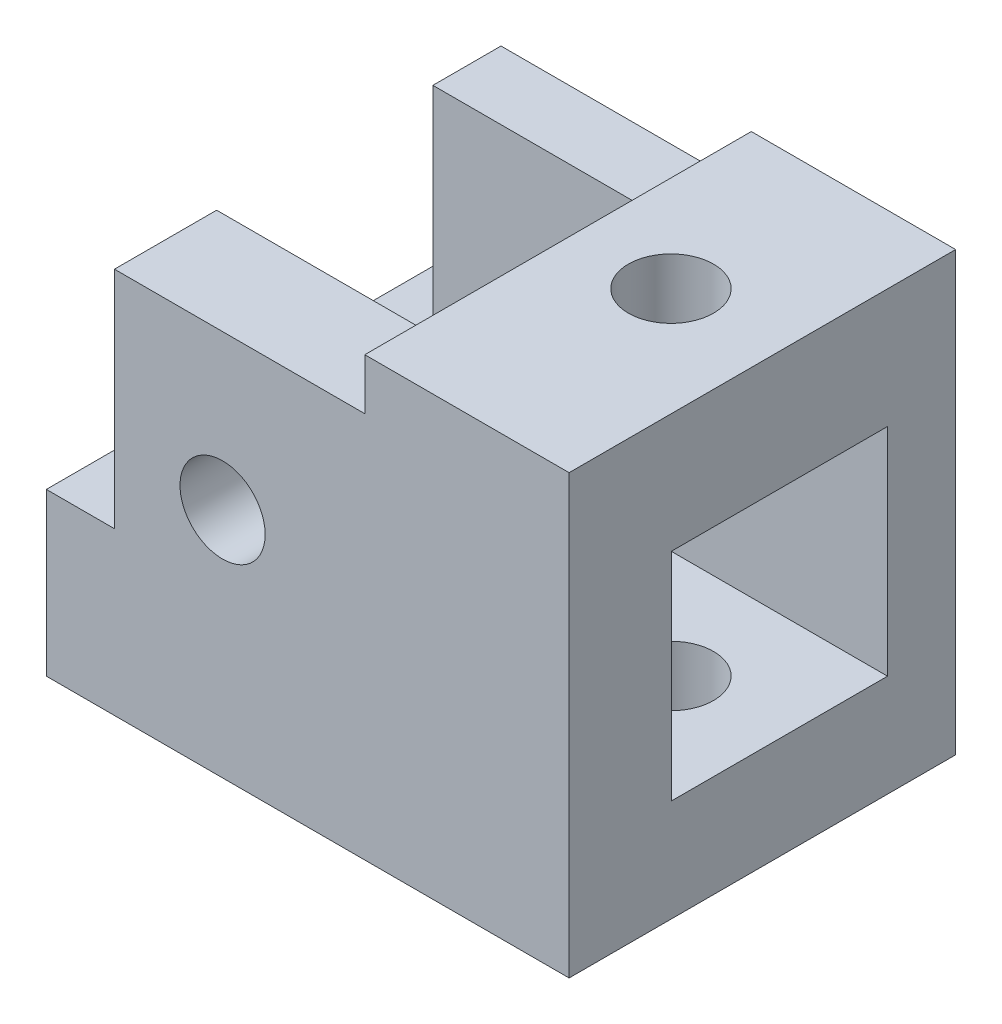
SolidWorks part; units mm, degrees
ref_plane "前视基准面" through (0, 0, 0) normal (0, 0, 1) x (1, 0, 0)
ref_plane "上视基准面" through (0, 0, 0) normal (0, 1, 0) x (1, 0, 0)
ref_plane "右视基准面" through (0, 0, 0) normal (1, 0, 0) x (0, 0, -1)
sketch "草图1" plane through (0, 0, 0) normal (0, 1, 0) x (1, 0, 0)
  line L0 (0, 18.7) -> (26.7, 18.7)
  line L1 (0, 0) -> (26.7, 0)
  line L2 (0, 0) -> (0, 22.7)
  line L3 (0, 22.7) -> (26.7, 22.7)
  line L4 (26.7, 0) -> (26.7, 22.7)
  line L5 (0, 6) -> (26.7, 6)
  dimension "D1" = 22.7
  dimension "D2" = 26.7
  dimension "D3" = 6
  dimension "D4" = 4
extrude "凸台-拉伸1" add sketch "草图1" against normal blind 6 contours L2 L5 L4 L0 | L5 L2 L1 L4 | L3 L4 L1 L2 region at (13.35, 0, -12.35) region at (13.35, 0, -3)
extrude "凸台-拉伸2" add sketch "草图1<3>" along normal blind 12.7 contours L5 L2 L1 L4 | L0 L4 L3 L2 region at (13.35, 0, -20.7) region at (13.35, 0, -3)
sketch "草图1<3>" plane through (0, 0, 0) normal (0, 1, 0) x (1, 0, 0) same geometry as "草图1"
sketch "草图2" plane through (0, 0, 0) normal (0, 0, 1) x (1, 0, 0)
  line L1 (0, -6) -> (0, 12.7) construction
  line L2 (0, 0) -> (26.7, 0) construction
  circle A0 centre (6.35, 7.63) radius 2.5
  dimension "D1" = 5
  dimension "D2" = 7.63
  dimension "D3" = 6.35
extrude "切除-拉伸1" cut sketch "草图2" against normal through all
sketch "草图3" plane through (0, 12.7, 0) normal (0, 1, 0) x (1, 0, 0)
  line L0 (0, 22.7) -> (0, 18.7)
  line L1 (0, 18.7) -> (12.7, 18.7)
  line L2 (0, 18.7) -> (26.7, 18.7) construction
  line L3 (12.7, 18.7) -> (12.7, 6)
  line L4 (0, 6) -> (26.7, 6) construction
  line L5 (12.7, 6) -> (0, 6)
  line L6 (0, 6) -> (0, 0)
  line L7 (0, 0) -> (26.7, 0)
  line L8 (26.7, 0) -> (26.7, 22.7)
  line L9 (26.7, 22.7) -> (0, 22.7)
  dimension "D1" = 12.7
extrude "凸台-拉伸3" add sketch "草图3" along normal blind 4
sketch "草图4" plane through (0, 16.7, 0) normal (0, 1, 0) x (1, 0, 0)
  line L0 (0, 18.7) -> (26.7, 18.7) construction
  line L1 (12.7, 18.7) -> (12.7, 6) construction
  circle A0 centre (20.33, 12.35) radius 2.5
  point P6 (18.3547, 9.8824)
  dimension "D1" = 5
  dimension "D2" = 6.35
  dimension "D3" = 7.63
extrude "切除-拉伸2" cut sketch "草图4" against normal through all
sketch "草图6" plane through (0, 0, 0) normal (-1, 0, 0) x (0, 0, 1)
  line L0 (-22.7, -6) -> (-22.7, 16.7) construction
  line L1 (0, -6) -> (-22.7, -6)
  line L2 (0, -6) -> (0, 3.5)
  line L3 (0, 3.5) -> (-22.7, 3.5)
  line L4 (-22.7, -6) -> (-22.7, 3.5)
  line L5 (-6, 0) -> (-18.7, 0) construction
  dimension "D1" = 3.5
extrude "凸台-拉伸4" add sketch "草图6" along normal blind 4
sketch "草图7" plane through (0, 16.7, 0) normal (0, 1, 0) x (1, 0, 0)
  line L0 (0, 0) -> (26.7, 0) construction
  line L1 (26.7, 22.7) -> (14.7, 22.7)
  line L2 (26.7, 22.7) -> (26.7, 0)
  line L3 (26.7, 0) -> (14.7, 0)
  line L4 (14.7, 22.7) -> (14.7, 0)
  circle A0 centre (20.33, 12.35) radius 2.5
  dimension "D2" = 5
  dimension "D1" = 12
extrude "凸台-拉伸5" add sketch "草图7" along normal blind 3
